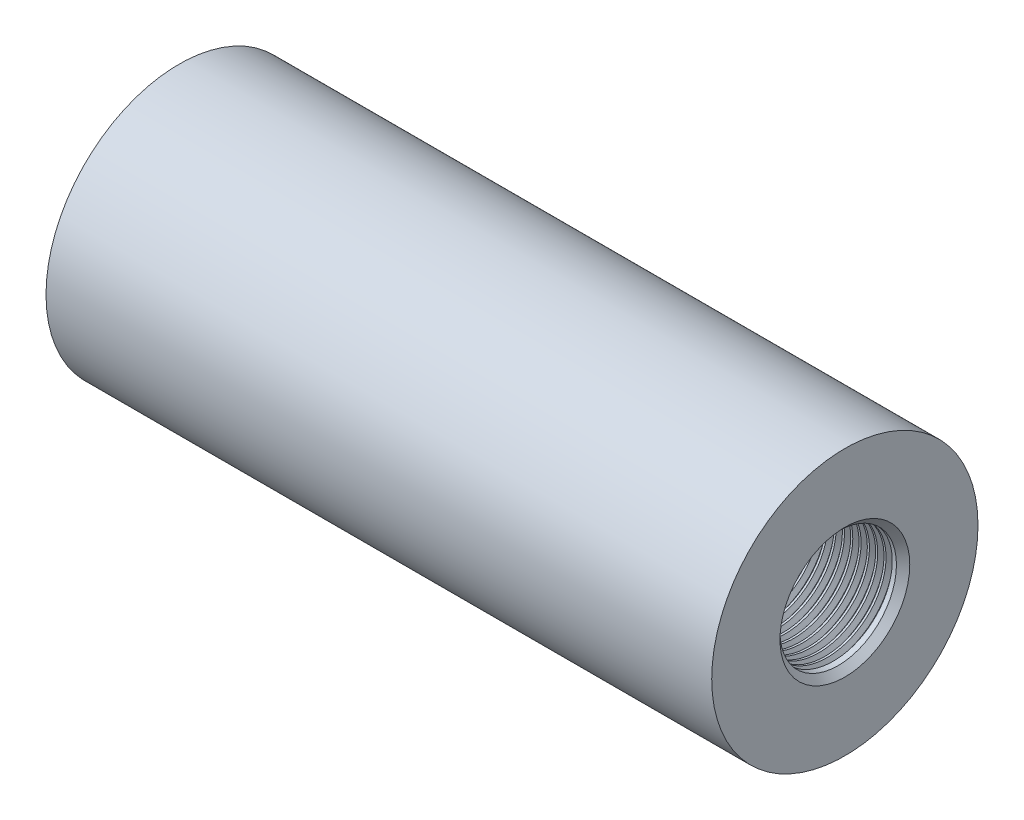
SolidWorks part; units mm, degrees
ref_plane "Front Plane" through (0, 0, 0) normal (0, 0, 1) x (1, 0, 0)
ref_plane "Top Plane" through (0, 0, 0) normal (0, 1, 0) x (1, 0, 0)
ref_plane "Right Plane" through (0, 0, 0) normal (1, 0, 0) x (0, 0, -1)
sketch "Sketch1" plane through (0, 0, 0) normal (1, 0, 0) x (0, 0, -1)
  circle A0 centre (0, 0) radius 4
  dimension "D1" = 8
extrude "Boss-Extrude1" add sketch "Sketch1" along normal blind 20
sketch "Sketch3" plane through (0, 0, 0) normal (-1, 0, 0) x (0, 0, 1)
  circle A0 centre (0, 0) radius 2
  dimension "D1" = 4
extrude "Cut-Extrude1" cut sketch "Sketch3" against normal blind 5
chamfer "Chamfer4" distance 0.2 angle 45 1 edges at (0, 0, 2)
thread "Thread1" pitch 0.25 method cut profile "Thread Profile3" start angle 0, offset 0, length 0, pitch 0.25, diameter 4
ref_plane "Plane4" through (0.2, 0, -2) normal (0, -1, 0) x (0, 0, -1)
sketch "Thread Profile3" plane through (0.2, 0, -2) normal (0, -1, 0) x (0, 0, -1)
  line L0 (0, 0) -> (0, 0.25) construction
  line L1 (0, 0) -> (0.1353, 0.0781)
  line L2 (0.1353, 0.0781) -> (0.1353, 0.1094)
  line L3 (0.1353, 0.1094) -> (0, 0.1875)
  line L4 (0.1353, 0.0937) -> (0, 0.0937) construction
  line L11 (0, 0) -> (0, 0.1875)
  point P2 (0, 0)
  dimension "Pitch" = 0.25
  dimension "Profile_Angle" = 60
  dimension "Profile_Land" = 0.0312
  dimension "Profile_Height" = 0.1353
sketch "Sketch15" plane through (20, 0, 0) normal (1, 0, 0) x (0, 0, -1)
  circle A0 centre (0, 0) radius 1.75
  dimension "D1" = 3.5
extrude "Cut-Extrude2" cut sketch "Sketch15" against normal blind 4
chamfer "Chamfer6" distance 0.2 angle 45 1 edges at (20, 0, -1.75)
thread "Thread3" pitch 0.25 method cut profile "Thread Profile5" start angle 0, offset 0, length 0, pitch 0.25, diameter 3.5
ref_plane "Plane6" through (19.8, 0, 1.75) normal (0, -1, 0) x (0, 0, 1)
sketch "Thread Profile5" plane through (19.8, 0, 1.75) normal (0, -1, 0) x (0, 0, 1)
  line L0 (0, 0) -> (0, 0.25) construction
  line L1 (0, 0) -> (0.1353, 0.0781)
  line L2 (0.1353, 0.0781) -> (0.1353, 0.1094)
  line L3 (0.1353, 0.1094) -> (0, 0.1875)
  line L4 (0.1353, 0.0937) -> (0, 0.0937) construction
  line L11 (0, 0) -> (0, 0.1875)
  point P2 (0, 0)
  dimension "Pitch" = 0.25
  dimension "Profile_Angle" = 60
  dimension "Profile_Land" = 0.0312
  dimension "Profile_Height" = 0.1353
